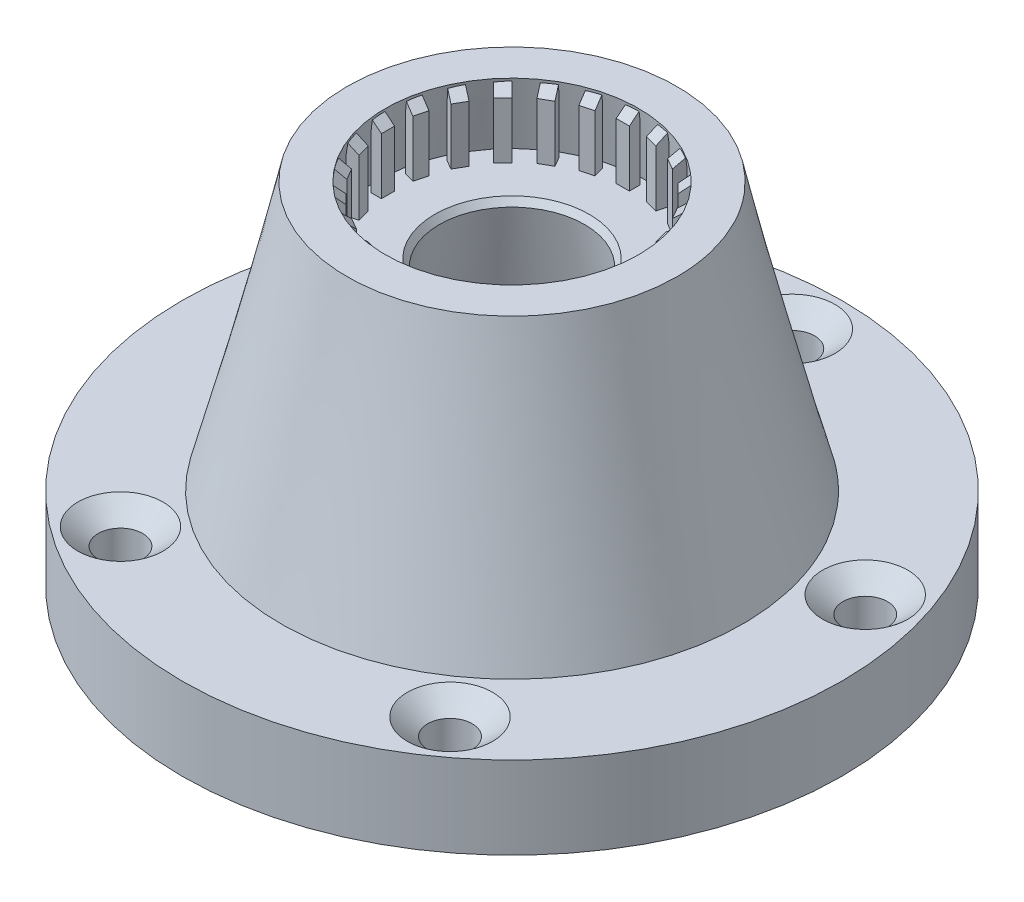
SolidWorks part; units mm, degrees
ref_plane "Front Plane" through (0, 0, 0) normal (0, 0, 1) x (1, 0, 0)
ref_plane "Top Plane" through (0, 0, 0) normal (0, 1, 0) x (1, 0, 0)
ref_plane "Right Plane" through (0, 0, 0) normal (1, 0, 0) x (0, 0, -1)
sketch "Sketch3" plane through (0, 0, 0) normal (0, 1, 0) x (1, 0, 0)
  circle A0 centre (0, 0) radius 100
ref_plane "Plane1" through (0, 106.1954, 0) normal (0, 1, 0) x (1, 0, 0)
extrude "Boss-Extrude1" add sketch "Sketch3" along normal blind 25
sketch "Sketch4" plane through (0, 25, 0) normal (0, 1, 0) x (1, 0, 0)
  circle A0 centre (0, 0) radius 70
sketch "Sketch5" plane through (0, 106.1954, 0) normal (0, 1, 0) x (1, 0, 0)
  circle A0 centre (0, 0) radius 50
loft "Loft1" add profiles "Sketch5", "Sketch4" connector at (-46.915, 106.1954, 17.2911) connector at (-57.4324, 25, 40.019)
sketch "Sketch7" plane through (0, 0, 0) normal (0, 0, 1) x (1, 0, 0)
  line L0 (0, 25) -> (0, 106.1954) construction
  line L1 (100, 25) -> (-100, 25) construction
  line L2 (50, 106.1954) -> (-50, 106.1954) construction
  line L3 (0, 65.5977) -> (0, 106.1954) construction
  line L4 (0, 65.5977) -> (0, 106.1954) construction
  line L5 (0, 85.8965) -> (-54.6114, 85.8965) construction
  line L6 (-27.3057, 85.8965) -> (-54.6114, 85.8965) construction
  line L7 (-27.3057, 85.8965) -> (-27.3057, 106.1954) construction
  line L8 (-27.3057, 106.1954) -> (-40.9586, 85.8965) construction
  line L9 (55, 106.1954) -> (-55, 106.1954) construction
  line L10 (-40.9586, 85.8965) -> (-38.4259, 106.1954)
  line L11 (-40.9586, 85.8965) -> (0, 85.8965)
  line L12 (0, 85.8965) -> (0, 106.1954)
  line L13 (0, 106.1954) -> (-38.4259, 106.1954)
  spline S0 degree 3 poles (-50, 106.1954) (-50.067, 105.8889) (-50.2282, 105.1512) (-50.4455, 104.1631) (-50.7531, 102.7698) (-51.2569, 100.5012) (-51.9697, 97.33) (-52.6244, 94.4566) (-53.091, 92.4258) (-53.3655, 91.2368) (-53.5875, 90.2788) (-53.7494, 89.5819) (-53.8918, 88.9699) (-54.0363, 88.3501) (-54.217, 87.5771) (-54.3916, 86.8318) (-54.6418, 85.7665) (-54.8638, 84.8247) (-55.0543, 84.0194) (-55.1292, 83.7028) (-55.1563, 83.5884) (-55.1791, 83.4926) (-55.2101, 83.3615) (-55.2515, 83.1869) (-55.3033, 82.9687) (-55.3646, 82.7104) (-55.435, 82.4141) (-55.5134, 82.0843) (-55.5996, 81.7223) (-55.6936, 81.328) (-55.7828, 80.9542) (-55.855, 80.6523) (-55.93, 80.3383) (-56.0281, 79.9284) (-56.1929, 79.2408) (-56.4111, 78.3322) (-56.5926, 77.5787) (-56.7099, 77.0925) (-56.8368, 76.5668) (-57.0974, 75.489) (-57.3534, 74.4349) (-57.5759, 73.5208) (-57.7344, 72.8704) (-57.92, 72.1107) (-58.0779, 71.4654) (-58.1944, 70.99) (-58.2935, 70.5858) (-58.3693, 70.2769) (-58.4408, 69.986) (-58.5723, 69.4509) (-58.7599, 68.6891) (-59.0135, 67.6615) (-59.298, 66.5115) (-59.5707, 65.4124) (-59.7988, 64.4954) (-59.9725, 63.798) (-60.1123, 63.2378) (-60.222, 62.7985) (-60.3092, 62.4496) (-60.4046, 62.0684) (-60.4887, 61.7322) (-60.5541, 61.471) (-60.6033, 61.2745) (-60.6553, 61.0672) (-60.71, 60.8491) (-60.7675, 60.6202) (-60.8282, 60.3783) (-60.8946, 60.1142) (-60.9695, 59.8159) (-61.0549, 59.4765) (-61.1379, 59.1467) (-61.211, 58.8564) (-61.2754, 58.6012) (-61.342, 58.3369) (-61.4158, 58.0443) (-61.4912, 57.7456) (-61.5659, 57.4496) (-61.6377, 57.1651) (-61.7274, 56.8105) (-61.8131, 56.472) (-61.8946, 56.15) (-61.958, 55.8999) (-62.0234, 55.6419) (-62.1055, 55.3185) (-62.1764, 55.0393) (-62.2379, 54.7968) (-62.3016, 54.5462) (-62.3979, 54.1672) (-62.522, 53.6795) (-62.631, 53.2513) (-62.7153, 52.9205) (-62.7799, 52.6671) (-62.8407, 52.4285) (-62.8978, 52.2047) (-62.9512, 51.9955) (-63.0015, 51.7988) (-63.0503, 51.608) (-63.0995, 51.4155) (-63.1675, 51.1493) (-63.2383, 50.8725) (-63.3049, 50.6123) (-63.349, 50.4402) (-63.4044, 50.2238) (-63.4932, 49.8771) (-63.619, 49.3864) (-63.7656, 48.8152) (-63.919, 48.2181) (-64.0471, 47.7203) (-64.1508, 47.3174) (-64.2311, 47.0058) (-64.3184, 46.6671) (-64.3989, 46.3549) (-64.4695, 46.0812) (-64.562, 45.7227) (-64.672, 45.2969) (-64.7915, 44.8343) (-64.8893, 44.4564) (-64.9824, 44.0966) (-65.0807, 43.7171) (-65.1842, 43.3177) (-65.2927, 42.8995) (-65.4039, 42.4709) (-65.5161, 42.039) (-65.6354, 41.5801) (-65.746, 41.1546) (-65.8524, 40.7459) (-65.95, 40.371) (-66.0585, 39.9544) (-66.1786, 39.4936) (-66.3129, 38.9787) (-66.4617, 38.4093) (-66.5865, 37.9322) (-66.6828, 37.564) (-66.7661, 37.2457) (-66.8437, 36.9492) (-66.9098, 36.6969) (-66.9518, 36.5366) (-67.0075, 36.324) (-67.0864, 36.0232) (-67.183, 35.6549) (-67.2835, 35.2719) (-67.3832, 34.8922) (-67.4786, 34.5289) (-67.5699, 34.1816) (-67.657, 33.8503) (-67.74, 33.5351) (-67.8188, 33.2358) (-67.8933, 32.9527) (-67.9637, 32.6861) (-68.0299, 32.4349) (-68.1098, 32.1319) (-68.1841, 31.85) (-68.253, 31.5893) (-68.3242, 31.3194) (-68.4026, 31.0224) (-68.4918, 30.6848) (-68.5694, 30.3915) (-68.6533, 30.0739) (-68.7439, 29.7314) (-68.8423, 29.3592) (-68.9512, 28.9481) (-69.0711, 28.4955) (-69.2025, 28.0002) (-69.32, 27.5577) (-69.4195, 27.1829) (-69.4969, 26.8914) (-69.5727, 26.6064) (-69.6493, 26.318) (-69.7257, 26.0306) (-69.8433, 25.5887) (-69.9342, 25.2472) (-70, 25) knots 0 0 0 0 0.011242 0.027064 0.036261 0.062383 0.110355 0.152756 0.16801 0.185036 0.196493 0.203257 0.210678 0.219013 0.22607 0.23913 0.24645 0.265289 0.273812 0.276108 0.276952 0.278026 0.279639 0.281792 0.284485 0.287714 0.29137 0.295416 0.29986 0.304709 0.309968 0.313704 0.315879 0.321535 0.32881 0.341222 0.355027 0.356589 0.359147 0.374411 0.396331 0.398026 0.408133 0.420324 0.426055 0.431948 0.437866 0.440972 0.44335 0.448602 0.460721 0.471467 0.486541 0.503181 0.512055 0.520407 0.528943 0.532747 0.536636 0.541836 0.546828 0.549123 0.551545 0.554096 0.556781 0.559603 0.562565 0.565747 0.569417 0.573599 0.578298 0.581605 0.584328 0.587733 0.591371 0.59517 0.598839 0.60235 0.605706 0.611959 0.614861 0.617619 0.621242 0.624449 0.629622 0.631589 0.633417 0.638889 0.645605 0.651451 0.654768 0.657896 0.660837 0.663595 0.666175 0.66858 0.670909 0.673291 0.675728 0.680776 0.683531 0.685357 0.687137 0.691552 0.698211 0.705326 0.712686 0.720301 0.723776 0.727621 0.731839 0.736311 0.739176 0.741971 0.74958 0.754965 0.759166 0.763605 0.768287 0.773217 0.778398 0.7838 0.789154 0.79441 0.800793 0.804911 0.809547 0.814706 0.820404 0.826737 0.833759 0.841498 0.844505 0.847486 0.853314 0.85549 0.856832 0.859256 0.863365 0.867975 0.872911 0.877615 0.882112 0.886405 0.890497 0.89439 0.898088 0.901596 0.904912 0.908027 0.910942 0.916174 0.918492 0.920613 0.926177 0.929501 0.933129 0.937064 0.941308 0.945892 0.95096 0.956549 0.962673 0.969342 0.973032 0.976642 0.980173 0.983609 0.987336 0.99083 1 1 1 1 construction
revolve "Cut-Revolve1" cut sketch "Sketch7" angle 360 about L0
sketch "Sketch9" plane through (0, 0, 0) normal (0, 0, 1) x (1, 0, 0)
  line L0 (0, 25) -> (0, 106.1954) construction
  line L1 (100, 25) -> (-100, 25) construction
  line L2 (50, 106.1954) -> (-50, 106.1954) construction
  line L3 (0, 65.5977) -> (0, 106.1954) construction
  line L4 (0, 85.8965) -> (0, 25)
  line L6 (-31.7854, 25) -> (-21.6872, 85.8965)
  line L7 (-21.6872, 85.8965) -> (0, 85.8965)
  line L8 (-31.7854, 25) -> (-35.931, 0)
  line L9 (-100, 0) -> (100, 0) construction
  line L10 (-35.931, 0) -> (-35.931, -8.2118)
  line L11 (-35.931, -8.2118) -> (0, -8.2118)
  line L12 (0, -8.2118) -> (0, 25)
  point P8 (-27.6124, 102.1465)
  point P16 (0, 0)
  point P17 (-41.3435, -8.9418)
  point P18 (-33.5342, 102.1465)
  point P19 (-27.1029, 102.1465)
  point P20 (-36.7498, -8.2118)
  point P21 (-20.4421, 102.1465)
  point P22 (0, 0)
  point P23 (-24.117, 102.1465)
  point P24 (-21.6872, 85.8965)
revolve "Cut-Revolve3" cut sketch "Sketch9" angle 360 about L0
sketch "Sketch10" plane through (0, 0, 0) normal (0, 0, 1) x (1, 0, 0)
  line L0 (0, 25) -> (0, 106.1954) construction
  line L1 (100, 25) -> (-100, 25) construction
  line L2 (50, 106.1954) -> (-50, 106.1954) construction
  line L3 (0, 65.5977) -> (0, 106.1954) construction
  line L4 (0, 106.1954) -> (0, 85.8965) construction
  line L5 (0, 85.8965) -> (-38.8103, 85.8965) construction
  line L6 (-38.8103, 85.8965) -> (-38.8103, 106.1954) construction
  line L8 (-38.8103, 85.8965) -> (-35.5964, 85.8965)
  line L9 (-35.5964, 85.8965) -> (-35.5964, 102.9734)
  line L11 (-35.5964, 102.9734) -> (-38.8103, 105.5649)
  line L12 (-38.8103, 105.5649) -> (-38.8103, 85.8965)
  point P7 (-35.5964, 102.9734)
extrude "Boss-Extrude2" add sketch "Sketch10" along normal blind 4
ref_axis "Axis1" through (0, 132.5052, 0) along (0, -1, 0)
pattern_circular "CirPattern1" count 24 every 15 about axis through (0, 132.5052, 0) along (0, -1, 0) of "Boss-Extrude2"
chamfer "Chamfer2" distance 2 angle 45 1 edges at (21.6872, 85.8965, 0) first distance on face at (35.931, 0, 0)
sketch "Sketch11" plane through (0, 25, 0) normal (0, 1, 0) x (1, 0, 0)
  line L0 (0, 0) -> (0, 100) construction
  line L1 (0, 100) -> (0, 70) construction
  circle A0 centre (0, 0) radius 100 construction
  circle A1 centre (0, 0) radius 70 construction
  circle A2 centre (0, 85) radius 10
  circle A3 centre (80.8398, 26.2664) radius 10
  circle A4 centre (49.9617, -68.7664) radius 10
  circle A5 centre (-49.9617, -68.7664) radius 10
  circle A6 centre (-80.8398, 26.2664) radius 10
  point P0 (0, 0)
  point P6 (0, 85)
  point P13 (80.8398, 26.2664)
  point P15 (49.9617, -68.7664)
  point P17 (-49.9617, -68.7664)
  point P19 (-80.8398, 26.2664)
  point P21 (0, 0)
  dimension "D1" = 5
hole_wizard "CSK for 1/2 Flat Head Machine Screw (100)1" positions "Sketch11" profile "Sketch12" countersink size "1/2" standard "ANSI Inch" end condition through all
sketch "Sketch12" plane through (0, 25, 0) normal (1, 0, 0) x (0, 0, 1)
  line L0 (0, 0) -> (0, 25)
  line L1 (0, 25) -> (6.7462, 25)
  line L2 (6.7462, 25) -> (6.7462, 5.177)
  line L3 (6.7462, 5.177) -> (12.9159, 0)
  line L5 (12.9159, 0) -> (0, 0)
  line L6 (-6.7462, 5.177) -> (-12.9159, 0) construction
  line L11 (0, -6.35) -> (0, 107.95) construction
  dimension "Thru Hole Dia." = 13.4925
  dimension "Thru Hole Depth" = 25
  dimension "Near C'Sink Dia." = 25.8318
  dimension "Near C'Sink Angle" = 100
